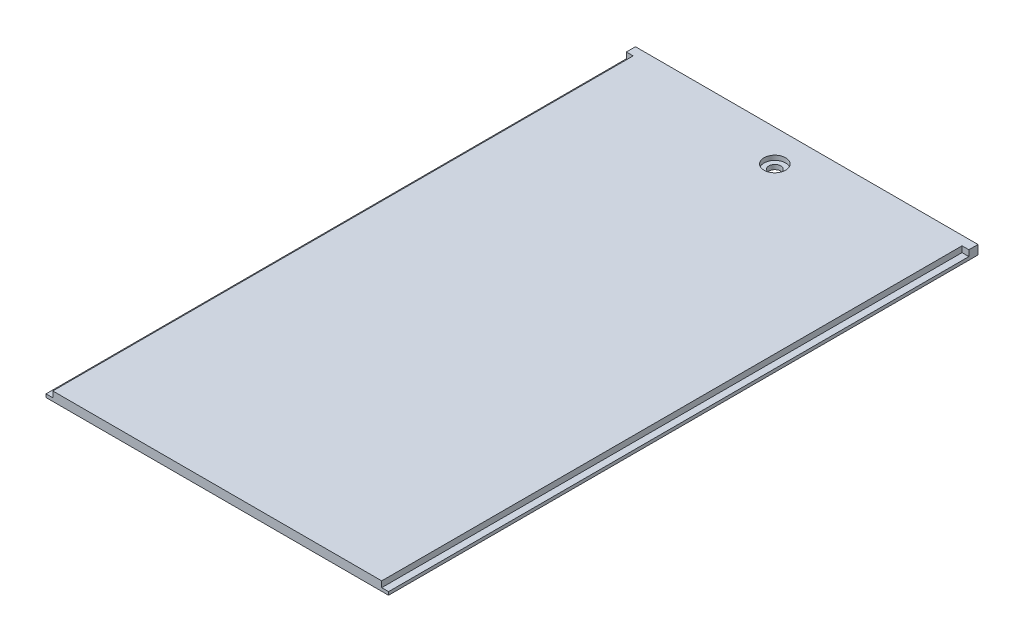
SolidWorks part; units mm, degrees
material "PLA"
ref_plane "Спереди" through (0, 0, 0) normal (0, 0, 1) x (1, 0, 0)
ref_plane "Сверху" through (0, 0, 0) normal (0, 1, 0) x (1, 0, 0)
ref_plane "Справа" through (0, 0, 0) normal (1, 0, 0) x (0, 0, -1)
sketch "Эскиз1" plane through (0, 0, 0) normal (0, 1, 0) x (1, 0, 0)
  line L1 (36.1, 63.7) -> (-36.1, 63.7)
  line L2 (36.1, 63.7) -> (36.1, -63.7)
  line L3 (36.1, -63.7) -> (-36.1, -63.7)
  line L4 (-36.1, 63.7) -> (-36.1, -63.7)
  line L5 (36.1, 63.7) -> (-36.1, -63.7) construction
  line L6 (36.1, -63.7) -> (-36.1, 63.7) construction
  point P0 (0, 0)
  dimension "D1" = 72.2
  dimension "D2" = 127.4
extrude "Бобышка-Вытянуть1" add sketch "Эскиз1" along normal blind 2
sketch "Эскиз2" plane through (0, 0, 63.7) normal (0, 0, 1) x (1, 0, 0)
  line L0 (0, 0) -> (0, -50000) construction
  line L1 (-36.1, 0) -> (-37.6, 0)
  line L2 (-36.1, 0) -> (-36.1, 0.7)
  line L3 (-36.1, 0.7) -> (-37.6, 0.7)
  line L4 (-37.6, 0) -> (-37.6, 0.7)
  line L5 (36.1, 0.7) -> (37.6, 0.7)
  line L6 (37.6, 0) -> (37.6, 0.7)
  line L7 (36.1, 0) -> (37.6, 0)
  line L8 (36.1, 0) -> (36.1, 0.7)
  dimension "D1" = 0.7
  dimension "D2" = 1.5
extrude "Бобышка-Вытянуть2" add sketch "Эскиз2" against normal up to surface (127.4 mm away) up to face at (0, 1, -63.7)
sketch "Эскиз3" plane through (0, 2, 0) normal (0, 1, 0) x (1, 0, 0)
  line L0 (0, 0) -> (0, 50000) construction
  line L1 (36.1, 63.7) -> (-36.1, 63.7) construction
  circle A0 centre (0, 58.7) radius 1.3
  dimension "D1" = 2.6
  dimension "D2" = 5
extrude "Вырез-Вытянуть1" cut sketch "Эскиз3" against normal through all
sketch "Эскиз5" plane through (0, 2, 0) normal (0, 1, 0) x (1, 0, 0)
  circle A0 centre (0, 58.7) radius 2.375
  dimension "D1" = 4.75
extrude "Вырез-Вытянуть2" cut sketch "Эскиз5" against normal blind 1
sketch "Эскиз6" plane through (0, 0, -63.7) normal (0, 0, -1) x (-1, 0, 0)
  line L0 (-36.1, 2) -> (36.1, 2) construction
  line L1 (-37.6, 0) -> (37.6, 0)
  line L2 (-37.6, 0) -> (-37.6, 2)
  line L3 (-37.6, 2) -> (37.6, 2)
  line L4 (37.6, 0) -> (37.6, 2)
  line L5 (-37.6, 0) -> (37.6, 0) construction
  point P8 (0, 0)
  dimension "D1" = 75.2
extrude "Бобышка-Вытянуть3" add sketch "Эскиз6" along normal blind 2
